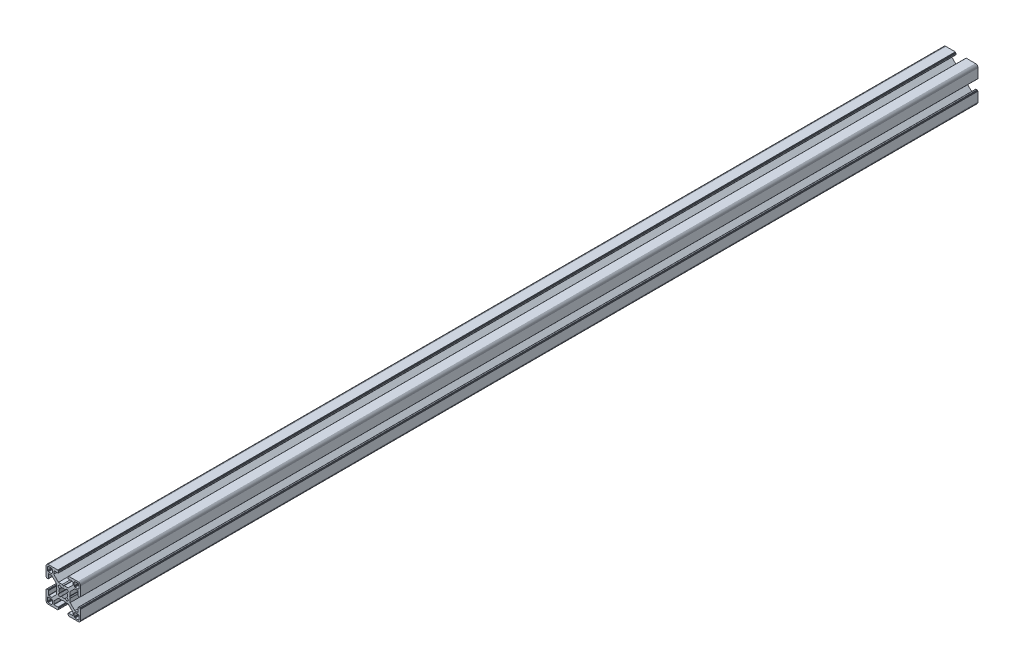
SolidWorks part; units mm, degrees
ref_plane "Front Plane" through (0, 0, 0) normal (0, 0, 1) x (1, 0, 0)
ref_plane "Top Plane" through (0, 0, 0) normal (0, 1, 0) x (1, 0, 0)
ref_plane "Right Plane" through (0, 0, 0) normal (1, 0, 0) x (0, 0, -1)
ref_plane "Plane1" through (0, 0, 0) normal (0, 0, 1) x (1, 0, 0)
sketch "Sketch1" plane through (0, 0, 0) normal (0, 0, 1) x (1, 0, 0)
  line L0 (28.3473, 29.9696) -> (28, 30)
  line L1 (28, 30) -> (19.75, 30)
  line L2 (19.75, 30) -> (19.7153, 29.997)
  line L3 (19.7153, 29.997) -> (19.6816, 29.9879)
  line L4 (19.6816, 29.9879) -> (19.65, 29.9732)
  line L5 (19.65, 29.9732) -> (19.6214, 29.9532)
  line L6 (19.6214, 29.9532) -> (19.5968, 29.9286)
  line L7 (19.5968, 29.9286) -> (19.5768, 29.9)
  line L8 (19.5768, 29.9) -> (19.5621, 29.8684)
  line L9 (19.5621, 29.8684) -> (19.553, 29.8347)
  line L10 (19.553, 29.8347) -> (19.55, 29.8)
  line L11 (19.55, 29.8) -> (19.55, 29.7)
  line L12 (19.55, 29.7) -> (19.547, 29.6653)
  line L13 (19.547, 29.6653) -> (19.5379, 29.6316)
  line L14 (19.5379, 29.6316) -> (19.5232, 29.6)
  line L15 (19.5232, 29.6) -> (19.5032, 29.5714)
  line L16 (19.5032, 29.5714) -> (19.4786, 29.5468)
  line L17 (19.4786, 29.5468) -> (19.45, 29.5268)
  line L18 (19.45, 29.5268) -> (19.4184, 29.5121)
  line L19 (19.4184, 29.5121) -> (19.3847, 29.503)
  line L20 (19.3847, 29.503) -> (19.35, 29.5)
  line L21 (19.35, 29.5) -> (19.25, 29.5)
  line L22 (19.25, 29.5) -> (19.2153, 29.497)
  line L23 (19.2153, 29.497) -> (19.1816, 29.4879)
  line L24 (19.1816, 29.4879) -> (19.15, 29.4732)
  line L25 (19.15, 29.4732) -> (19.1214, 29.4532)
  line L26 (19.1214, 29.4532) -> (19.0968, 29.4286)
  line L27 (19.0968, 29.4286) -> (19.0768, 29.4)
  line L28 (19.0768, 29.4) -> (19.0621, 29.3684)
  line L29 (19.0621, 29.3684) -> (19.053, 29.3347)
  line L30 (19.053, 29.3347) -> (19.05, 29.3)
  line L31 (19.05, 29.3) -> (19.05, 28.4)
  line L32 (19.05, 28.4) -> (19.0591, 28.2958)
  line L33 (19.0591, 28.2958) -> (19.0862, 28.1948)
  line L34 (19.0862, 28.1948) -> (19.1304, 28.1)
  line L35 (19.1304, 28.1) -> (19.1904, 28.0143)
  line L36 (19.1904, 28.0143) -> (19.2643, 27.9404)
  line L37 (19.2643, 27.9404) -> (19.35, 27.8804)
  line L38 (19.35, 27.8804) -> (19.4448, 27.8362)
  line L39 (19.4448, 27.8362) -> (19.5458, 27.8091)
  line L40 (19.5458, 27.8091) -> (19.65, 27.8)
  line L41 (19.65, 27.8) -> (23.05, 27.8)
  line L42 (23.05, 27.8) -> (23.0847, 27.7969)
  line L43 (23.0847, 27.7969) -> (23.1184, 27.7879)
  line L44 (23.1184, 27.7879) -> (23.15, 27.7732)
  line L45 (23.15, 27.7732) -> (23.1786, 27.7532)
  line L46 (23.1786, 27.7532) -> (23.2032, 27.7285)
  line L47 (23.2032, 27.7285) -> (23.2232, 27.7)
  line L48 (23.2232, 27.7) -> (23.2379, 27.6684)
  line L49 (23.2379, 27.6684) -> (23.247, 27.6347)
  line L50 (23.247, 27.6347) -> (23.25, 27.6)
  line L51 (23.25, 27.6) -> (23.25, 25.05)
  line L52 (23.25, 25.05) -> (19.2045, 21)
  line L53 (19.2045, 21) -> (15.9, 21)
  line L54 (15.9, 21) -> (15, 20.4848)
  line L55 (15, 20.4848) -> (14.1, 21)
  line L56 (14.1, 21) -> (10.7955, 21)
  line L57 (10.7955, 21) -> (7.9973, 23.8013)
  line L58 (7.9973, 23.8013) -> (6.75, 25.05)
  line L59 (6.75, 25.05) -> (6.75, 27.6)
  line L60 (6.75, 27.6) -> (6.753, 27.6347)
  line L61 (6.753, 27.6347) -> (6.7621, 27.6684)
  line L62 (6.7621, 27.6684) -> (6.7768, 27.7)
  line L63 (6.7768, 27.7) -> (6.7968, 27.7285)
  line L64 (6.7968, 27.7285) -> (6.8215, 27.7532)
  line L65 (6.8215, 27.7532) -> (6.85, 27.7732)
  line L66 (6.85, 27.7732) -> (6.8816, 27.7879)
  line L67 (6.8816, 27.7879) -> (6.9153, 27.7969)
  line L68 (6.9153, 27.7969) -> (6.95, 27.8)
  line L69 (6.95, 27.8) -> (10.35, 27.8)
  line L70 (10.35, 27.8) -> (10.4542, 27.8091)
  line L71 (10.4542, 27.8091) -> (10.5552, 27.8362)
  line L72 (10.5552, 27.8362) -> (10.65, 27.8804)
  line L73 (10.65, 27.8804) -> (10.7357, 27.9404)
  line L74 (10.7357, 27.9404) -> (10.8096, 28.0143)
  line L75 (10.8096, 28.0143) -> (10.8696, 28.1)
  line L76 (10.8696, 28.1) -> (10.9138, 28.1948)
  line L77 (10.9138, 28.1948) -> (10.9409, 28.2958)
  line L78 (10.9409, 28.2958) -> (10.95, 28.4)
  line L79 (10.95, 28.4) -> (10.95, 29.3)
  line L80 (10.95, 29.3) -> (10.947, 29.3347)
  line L81 (10.947, 29.3347) -> (10.938, 29.3684)
  line L82 (10.938, 29.3684) -> (10.9232, 29.4)
  line L83 (10.9232, 29.4) -> (10.9032, 29.4286)
  line L84 (10.9032, 29.4286) -> (10.8786, 29.4532)
  line L85 (10.8786, 29.4532) -> (10.85, 29.4732)
  line L86 (10.85, 29.4732) -> (10.8184, 29.4879)
  line L87 (10.8184, 29.4879) -> (10.7847, 29.497)
  line L88 (10.7847, 29.497) -> (10.75, 29.5)
  line L89 (10.75, 29.5) -> (10.65, 29.5)
  line L90 (10.65, 29.5) -> (10.6153, 29.503)
  line L91 (10.6153, 29.503) -> (10.5816, 29.5121)
  line L92 (10.5816, 29.5121) -> (10.55, 29.5268)
  line L93 (10.55, 29.5268) -> (10.5214, 29.5468)
  line L94 (10.5214, 29.5468) -> (10.4968, 29.5714)
  line L95 (10.4968, 29.5714) -> (10.4768, 29.6)
  line L96 (10.4768, 29.6) -> (10.4621, 29.6316)
  line L97 (10.4621, 29.6316) -> (10.453, 29.6653)
  line L98 (10.453, 29.6653) -> (10.45, 29.7)
  line L99 (10.45, 29.7) -> (10.45, 29.8)
  line L100 (10.45, 29.8) -> (10.447, 29.8347)
  line L101 (10.447, 29.8347) -> (10.4379, 29.8684)
  line L102 (10.4379, 29.8684) -> (10.4232, 29.9)
  line L103 (10.4232, 29.9) -> (10.4032, 29.9286)
  line L104 (10.4032, 29.9286) -> (10.3786, 29.9532)
  line L105 (10.3786, 29.9532) -> (10.35, 29.9732)
  line L106 (10.35, 29.9732) -> (10.3184, 29.9879)
  line L107 (10.3184, 29.9879) -> (10.2847, 29.997)
  line L108 (10.2847, 29.997) -> (10.25, 30)
  line L109 (10.25, 30) -> (2, 30)
  line L110 (2, 30) -> (1.6527, 29.9696)
  line L111 (1.6527, 29.9696) -> (1.316, 29.8794)
  line L112 (1.316, 29.8794) -> (1, 29.7321)
  line L113 (1, 29.7321) -> (0.7144, 29.5321)
  line L114 (0.7144, 29.5321) -> (0.4679, 29.2856)
  line L115 (0.4679, 29.2856) -> (0.2679, 29)
  line L116 (0.2679, 29) -> (0.1206, 28.684)
  line L117 (0.1206, 28.684) -> (0.0304, 28.3473)
  line L118 (0.0304, 28.3473) -> (0, 28)
  line L119 (0, 28) -> (0, 19.75)
  line L120 (0, 19.75) -> (0.003, 19.7153)
  line L121 (0.003, 19.7153) -> (0.0121, 19.6816)
  line L122 (0.0121, 19.6816) -> (0.0268, 19.65)
  line L123 (0.0268, 19.65) -> (0.0468, 19.6214)
  line L124 (0.0468, 19.6214) -> (0.0714, 19.5968)
  line L125 (0.0714, 19.5968) -> (0.1, 19.5768)
  line L126 (0.1, 19.5768) -> (0.1316, 19.5621)
  line L127 (0.1316, 19.5621) -> (0.1653, 19.553)
  line L128 (0.1653, 19.553) -> (0.2, 19.55)
  line L129 (0.2, 19.55) -> (0.3, 19.55)
  line L130 (0.3, 19.55) -> (0.3347, 19.547)
  line L131 (0.3347, 19.547) -> (0.3684, 19.5379)
  line L132 (0.3684, 19.5379) -> (0.4, 19.5232)
  line L133 (0.4, 19.5232) -> (0.4286, 19.5032)
  line L134 (0.4286, 19.5032) -> (0.4532, 19.4786)
  line L135 (0.4532, 19.4786) -> (0.4732, 19.45)
  line L136 (0.4732, 19.45) -> (0.4879, 19.4184)
  line L137 (0.4879, 19.4184) -> (0.497, 19.3847)
  line L138 (0.497, 19.3847) -> (0.5, 19.35)
  line L139 (0.5, 19.35) -> (0.5, 19.25)
  line L140 (0.5, 19.25) -> (0.503, 19.2153)
  line L141 (0.503, 19.2153) -> (0.5121, 19.1816)
  line L142 (0.5121, 19.1816) -> (0.5268, 19.15)
  line L143 (0.5268, 19.15) -> (0.5468, 19.1214)
  line L144 (0.5468, 19.1214) -> (0.5714, 19.0968)
  line L145 (0.5714, 19.0968) -> (0.6, 19.0768)
  line L146 (0.6, 19.0768) -> (0.6316, 19.0621)
  line L147 (0.6316, 19.0621) -> (0.6653, 19.053)
  line L148 (0.6653, 19.053) -> (0.7, 19.05)
  line L149 (0.7, 19.05) -> (1.6, 19.05)
  line L150 (1.6, 19.05) -> (1.7042, 19.0591)
  line L151 (1.7042, 19.0591) -> (1.8052, 19.0862)
  line L152 (1.8052, 19.0862) -> (1.9, 19.1304)
  line L153 (1.9, 19.1304) -> (1.9857, 19.1904)
  line L154 (1.9857, 19.1904) -> (2.0596, 19.2643)
  line L155 (2.0596, 19.2643) -> (2.1196, 19.35)
  line L156 (2.1196, 19.35) -> (2.1638, 19.4448)
  line L157 (2.1638, 19.4448) -> (2.1909, 19.5458)
  line L158 (2.1909, 19.5458) -> (2.2, 19.65)
  line L159 (2.2, 19.65) -> (2.2, 23.05)
  line L160 (2.2, 23.05) -> (2.203, 23.0847)
  line L161 (2.203, 23.0847) -> (2.2121, 23.1184)
  line L162 (2.2121, 23.1184) -> (2.2268, 23.15)
  line L163 (2.2268, 23.15) -> (2.2468, 23.1786)
  line L164 (2.2468, 23.1786) -> (2.2714, 23.2032)
  line L165 (2.2714, 23.2032) -> (2.3, 23.2232)
  line L166 (2.3, 23.2232) -> (2.3316, 23.2379)
  line L167 (2.3316, 23.2379) -> (2.3653, 23.247)
  line L168 (2.3653, 23.247) -> (2.4, 23.25)
  line L169 (2.4, 23.25) -> (4.95, 23.25)
  line L170 (4.95, 23.25) -> (7.9973, 20.2027)
  line L171 (7.9973, 20.2027) -> (8.9955, 19.2045)
  line L172 (8.9955, 19.2045) -> (8.9955, 15.9)
  line L173 (8.9955, 15.9) -> (9.5151, 15)
  line L174 (9.5151, 15) -> (8.9955, 14.1)
  line L175 (8.9955, 14.1) -> (8.9955, 10.7955)
  line L176 (8.9955, 10.7955) -> (4.95, 6.75)
  line L177 (4.95, 6.75) -> (2.4, 6.75)
  line L178 (2.4, 6.75) -> (2.3653, 6.753)
  line L179 (2.3653, 6.753) -> (2.3316, 6.7621)
  line L180 (2.3316, 6.7621) -> (2.3, 6.7768)
  line L181 (2.3, 6.7768) -> (2.2714, 6.7968)
  line L182 (2.2714, 6.7968) -> (2.2468, 6.8214)
  line L183 (2.2468, 6.8214) -> (2.2268, 6.85)
  line L184 (2.2268, 6.85) -> (2.2121, 6.8816)
  line L185 (2.2121, 6.8816) -> (2.203, 6.9153)
  line L186 (2.203, 6.9153) -> (2.2, 6.95)
  line L187 (2.2, 6.95) -> (2.2, 10.35)
  line L188 (2.2, 10.35) -> (2.1909, 10.4542)
  line L189 (2.1909, 10.4542) -> (2.1638, 10.5552)
  line L190 (2.1638, 10.5552) -> (2.1196, 10.65)
  line L191 (2.1196, 10.65) -> (2.0596, 10.7357)
  line L192 (2.0596, 10.7357) -> (1.9857, 10.8096)
  line L193 (1.9857, 10.8096) -> (1.9, 10.8696)
  line L194 (1.9, 10.8696) -> (1.8052, 10.9138)
  line L195 (1.8052, 10.9138) -> (1.7042, 10.9409)
  line L196 (1.7042, 10.9409) -> (1.6, 10.95)
  line L197 (1.6, 10.95) -> (0.7, 10.95)
  line L198 (0.7, 10.95) -> (0.6653, 10.9469)
  line L199 (0.6653, 10.9469) -> (0.6316, 10.9379)
  line L200 (0.6316, 10.9379) -> (0.6, 10.9232)
  line L201 (0.6, 10.9232) -> (0.5715, 10.9032)
  line L202 (0.5715, 10.9032) -> (0.5468, 10.8785)
  line L203 (0.5468, 10.8785) -> (0.5268, 10.85)
  line L204 (0.5268, 10.85) -> (0.5121, 10.8184)
  line L205 (0.5121, 10.8184) -> (0.503, 10.7847)
  line L206 (0.503, 10.7847) -> (0.5, 10.75)
  line L207 (0.5, 10.75) -> (0.5, 10.65)
  line L208 (0.5, 10.65) -> (0.497, 10.6153)
  line L209 (0.497, 10.6153) -> (0.4879, 10.5816)
  line L210 (0.4879, 10.5816) -> (0.4732, 10.55)
  line L211 (0.4732, 10.55) -> (0.4532, 10.5214)
  line L212 (0.4532, 10.5214) -> (0.4286, 10.4968)
  line L213 (0.4286, 10.4968) -> (0.4, 10.4768)
  line L214 (0.4, 10.4768) -> (0.3684, 10.4621)
  line L215 (0.3684, 10.4621) -> (0.3347, 10.453)
  line L216 (0.3347, 10.453) -> (0.3, 10.45)
  line L217 (0.3, 10.45) -> (0.2, 10.45)
  line L218 (0.2, 10.45) -> (0.1653, 10.447)
  line L219 (0.1653, 10.447) -> (0.1316, 10.4379)
  line L220 (0.1316, 10.4379) -> (0.1, 10.4232)
  line L221 (0.1, 10.4232) -> (0.0714, 10.4032)
  line L222 (0.0714, 10.4032) -> (0.0468, 10.3786)
  line L223 (0.0468, 10.3786) -> (0.0268, 10.35)
  line L224 (0.0268, 10.35) -> (0.0121, 10.3184)
  line L225 (0.0121, 10.3184) -> (0.003, 10.2847)
  line L226 (0.003, 10.2847) -> (0, 10.25)
  line L227 (0, 10.25) -> (0, 2)
  line L228 (0, 2) -> (0.0304, 1.6527)
  line L229 (0.0304, 1.6527) -> (0.1206, 1.316)
  line L230 (0.1206, 1.316) -> (0.2679, 1)
  line L231 (0.2679, 1) -> (0.4679, 0.7144)
  line L232 (0.4679, 0.7144) -> (0.7144, 0.4679)
  line L233 (0.7144, 0.4679) -> (1, 0.2679)
  line L234 (1, 0.2679) -> (1.316, 0.1206)
  line L235 (1.316, 0.1206) -> (1.6527, 0.0304)
  line L236 (1.6527, 0.0304) -> (2, 0)
  line L237 (2, 0) -> (10.25, 0)
  line L238 (10.25, 0) -> (10.2847, 0.003)
  line L239 (10.2847, 0.003) -> (10.3184, 0.0121)
  line L240 (10.3184, 0.0121) -> (10.35, 0.0268)
  line L241 (10.35, 0.0268) -> (10.3786, 0.0468)
  line L242 (10.3786, 0.0468) -> (10.4032, 0.0714)
  line L243 (10.4032, 0.0714) -> (10.4232, 0.1)
  line L244 (10.4232, 0.1) -> (10.4379, 0.1316)
  line L245 (10.4379, 0.1316) -> (10.447, 0.1653)
  line L246 (10.447, 0.1653) -> (10.45, 0.2)
  line L247 (10.45, 0.2) -> (10.45, 0.3)
  line L248 (10.45, 0.3) -> (10.453, 0.3347)
  line L249 (10.453, 0.3347) -> (10.4621, 0.3684)
  line L250 (10.4621, 0.3684) -> (10.4768, 0.4)
  line L251 (10.4768, 0.4) -> (10.4968, 0.4286)
  line L252 (10.4968, 0.4286) -> (10.5214, 0.4532)
  line L253 (10.5214, 0.4532) -> (10.55, 0.4732)
  line L254 (10.55, 0.4732) -> (10.5816, 0.4879)
  line L255 (10.5816, 0.4879) -> (10.6153, 0.497)
  line L256 (10.6153, 0.497) -> (10.65, 0.5)
  line L257 (10.65, 0.5) -> (10.75, 0.5)
  line L258 (10.75, 0.5) -> (10.7847, 0.503)
  line L259 (10.7847, 0.503) -> (10.8184, 0.5121)
  line L260 (10.8184, 0.5121) -> (10.85, 0.5268)
  line L261 (10.85, 0.5268) -> (10.8785, 0.5468)
  line L262 (10.8785, 0.5468) -> (10.9032, 0.5715)
  line L263 (10.9032, 0.5715) -> (10.9232, 0.6)
  line L264 (10.9232, 0.6) -> (10.9379, 0.6316)
  line L265 (10.9379, 0.6316) -> (10.9469, 0.6653)
  line L266 (10.9469, 0.6653) -> (10.95, 0.7)
  line L267 (10.95, 0.7) -> (10.95, 1.6)
  line L268 (10.95, 1.6) -> (10.9409, 1.7042)
  line L269 (10.9409, 1.7042) -> (10.9138, 1.8052)
  line L270 (10.9138, 1.8052) -> (10.8696, 1.9)
  line L271 (10.8696, 1.9) -> (10.8096, 1.9857)
  line L272 (10.8096, 1.9857) -> (10.7357, 2.0596)
  line L273 (10.7357, 2.0596) -> (10.65, 2.1196)
  line L274 (10.65, 2.1196) -> (10.5552, 2.1638)
  line L275 (10.5552, 2.1638) -> (10.4542, 2.1909)
  line L276 (10.4542, 2.1909) -> (10.35, 2.2)
  line L277 (10.35, 2.2) -> (6.95, 2.2)
  line L278 (6.95, 2.2) -> (6.9153, 2.203)
  line L279 (6.9153, 2.203) -> (6.8816, 2.212)
  line L280 (6.8816, 2.212) -> (6.85, 2.2268)
  line L281 (6.85, 2.2268) -> (6.8215, 2.2468)
  line L282 (6.8215, 2.2468) -> (6.7968, 2.2714)
  line L283 (6.7968, 2.2714) -> (6.7768, 2.3)
  line L284 (6.7768, 2.3) -> (6.7621, 2.3316)
  line L285 (6.7621, 2.3316) -> (6.753, 2.3653)
  line L286 (6.753, 2.3653) -> (6.75, 2.4)
  line L287 (6.75, 2.4) -> (6.75, 4.95)
  line L288 (6.75, 4.95) -> (9.7875, 7.9908)
  line L289 (9.7875, 7.9908) -> (10.7955, 9)
  line L290 (10.7955, 9) -> (14.1, 9)
  line L291 (14.1, 9) -> (15, 9.5151)
  line L292 (15, 9.5151) -> (15.9, 9)
  line L293 (15.9, 9) -> (19.2045, 9)
  line L294 (19.2045, 9) -> (20.2126, 7.9908)
  line L295 (20.2126, 7.9908) -> (23.25, 4.95)
  line L296 (23.25, 4.95) -> (23.25, 2.4)
  line L297 (23.25, 2.4) -> (23.247, 2.3653)
  line L298 (23.247, 2.3653) -> (23.2379, 2.3316)
  line L299 (23.2379, 2.3316) -> (23.2232, 2.3)
  line L300 (23.2232, 2.3) -> (23.2032, 2.2714)
  line L301 (23.2032, 2.2714) -> (23.1786, 2.2468)
  line L302 (23.1786, 2.2468) -> (23.15, 2.2268)
  line L303 (23.15, 2.2268) -> (23.1184, 2.212)
  line L304 (23.1184, 2.212) -> (23.0847, 2.203)
  line L305 (23.0847, 2.203) -> (23.05, 2.2)
  line L306 (23.05, 2.2) -> (19.65, 2.2)
  line L307 (19.65, 2.2) -> (19.5458, 2.1909)
  line L308 (19.5458, 2.1909) -> (19.4448, 2.1638)
  line L309 (19.4448, 2.1638) -> (19.35, 2.1196)
  line L310 (19.35, 2.1196) -> (19.2643, 2.0596)
  line L311 (19.2643, 2.0596) -> (19.1904, 1.9857)
  line L312 (19.1904, 1.9857) -> (19.1304, 1.9)
  line L313 (19.1304, 1.9) -> (19.0862, 1.8052)
  line L314 (19.0862, 1.8052) -> (19.0591, 1.7042)
  line L315 (19.0591, 1.7042) -> (19.05, 1.6)
  line L316 (19.05, 1.6) -> (19.05, 0.7)
  line L317 (19.05, 0.7) -> (19.053, 0.6653)
  line L318 (19.053, 0.6653) -> (19.0621, 0.6316)
  line L319 (19.0621, 0.6316) -> (19.0768, 0.6)
  line L320 (19.0768, 0.6) -> (19.0968, 0.5714)
  line L321 (19.0968, 0.5714) -> (19.1214, 0.5468)
  line L322 (19.1214, 0.5468) -> (19.15, 0.5268)
  line L323 (19.15, 0.5268) -> (19.1816, 0.5121)
  line L324 (19.1816, 0.5121) -> (19.2153, 0.503)
  line L325 (19.2153, 0.503) -> (19.25, 0.5)
  line L326 (19.25, 0.5) -> (19.35, 0.5)
  line L327 (19.35, 0.5) -> (19.3847, 0.497)
  line L328 (19.3847, 0.497) -> (19.4184, 0.4879)
  line L329 (19.4184, 0.4879) -> (19.45, 0.4732)
  line L330 (19.45, 0.4732) -> (19.4786, 0.4532)
  line L331 (19.4786, 0.4532) -> (19.5032, 0.4286)
  line L332 (19.5032, 0.4286) -> (19.5232, 0.4)
  line L333 (19.5232, 0.4) -> (19.5379, 0.3684)
  line L334 (19.5379, 0.3684) -> (19.547, 0.3347)
  line L335 (19.547, 0.3347) -> (19.55, 0.3)
  line L336 (19.55, 0.3) -> (19.55, 0.2)
  line L337 (19.55, 0.2) -> (19.553, 0.1653)
  line L338 (19.553, 0.1653) -> (19.5621, 0.1316)
  line L339 (19.5621, 0.1316) -> (19.5768, 0.1)
  line L340 (19.5768, 0.1) -> (19.5968, 0.0714)
  line L341 (19.5968, 0.0714) -> (19.6214, 0.0468)
  line L342 (19.6214, 0.0468) -> (19.65, 0.0268)
  line L343 (19.65, 0.0268) -> (19.6816, 0.0121)
  line L344 (19.6816, 0.0121) -> (19.7153, 0.003)
  line L345 (19.7153, 0.003) -> (19.75, 0)
  line L346 (19.75, 0) -> (28, 0)
  line L347 (28, 0) -> (28.3473, 0.0304)
  line L348 (28.3473, 0.0304) -> (28.684, 0.1206)
  line L349 (28.684, 0.1206) -> (29, 0.2679)
  line L350 (29, 0.2679) -> (29.2856, 0.4679)
  line L351 (29.2856, 0.4679) -> (29.5321, 0.7144)
  line L352 (29.5321, 0.7144) -> (29.7321, 1)
  line L353 (29.7321, 1) -> (29.8794, 1.316)
  line L354 (29.8794, 1.316) -> (29.9696, 1.6527)
  line L355 (29.9696, 1.6527) -> (30, 2)
  line L356 (30, 2) -> (30, 10.25)
  line L357 (30, 10.25) -> (29.997, 10.2847)
  line L358 (29.997, 10.2847) -> (29.988, 10.3184)
  line L359 (29.988, 10.3184) -> (29.9732, 10.35)
  line L360 (29.9732, 10.35) -> (29.9532, 10.3785)
  line L361 (29.9532, 10.3785) -> (29.9286, 10.4032)
  line L362 (29.9286, 10.4032) -> (29.9, 10.4232)
  line L363 (29.9, 10.4232) -> (29.8684, 10.4379)
  line L364 (29.8684, 10.4379) -> (29.8347, 10.447)
  line L365 (29.8347, 10.447) -> (29.8, 10.45)
  line L366 (29.8, 10.45) -> (29.7, 10.45)
  line L367 (29.7, 10.45) -> (29.6649, 10.4534)
  line L368 (29.6649, 10.4534) -> (29.6312, 10.4624)
  line L369 (29.6312, 10.4624) -> (29.5996, 10.4772)
  line L370 (29.5996, 10.4772) -> (29.5711, 10.4972)
  line L371 (29.5711, 10.4972) -> (29.5464, 10.5218)
  line L372 (29.5464, 10.5218) -> (29.5264, 10.5504)
  line L373 (29.5264, 10.5504) -> (29.5117, 10.582)
  line L374 (29.5117, 10.582) -> (29.5027, 10.6156)
  line L375 (29.5027, 10.6156) -> (29.4996, 10.6504)
  line L376 (29.4996, 10.6504) -> (29.4996, 10.7504)
  line L377 (29.4996, 10.7504) -> (29.497, 10.7847)
  line L378 (29.497, 10.7847) -> (29.4879, 10.8184)
  line L379 (29.4879, 10.8184) -> (29.4732, 10.85)
  line L380 (29.4732, 10.85) -> (29.4532, 10.8785)
  line L381 (29.4532, 10.8785) -> (29.4286, 10.9032)
  line L382 (29.4286, 10.9032) -> (29.4, 10.9232)
  line L383 (29.4, 10.9232) -> (29.3684, 10.9379)
  line L384 (29.3684, 10.9379) -> (29.3347, 10.9469)
  line L385 (29.3347, 10.9469) -> (29.3, 10.95)
  line L386 (29.3, 10.95) -> (28.4, 10.95)
  line L387 (28.4, 10.95) -> (28.2958, 10.9409)
  line L388 (28.2958, 10.9409) -> (28.1948, 10.9138)
  line L389 (28.1948, 10.9138) -> (28.1, 10.8696)
  line L390 (28.1, 10.8696) -> (28.0143, 10.8096)
  line L391 (28.0143, 10.8096) -> (27.9404, 10.7357)
  line L392 (27.9404, 10.7357) -> (27.8804, 10.65)
  line L393 (27.8804, 10.65) -> (27.8362, 10.5552)
  line L394 (27.8362, 10.5552) -> (27.8091, 10.4542)
  line L395 (27.8091, 10.4542) -> (27.8, 10.35)
  line L396 (27.8, 10.35) -> (27.8, 6.95)
  line L397 (27.8, 6.95) -> (27.797, 6.9153)
  line L398 (27.797, 6.9153) -> (27.7879, 6.8816)
  line L399 (27.7879, 6.8816) -> (27.7732, 6.85)
  line L400 (27.7732, 6.85) -> (27.7532, 6.8214)
  line L401 (27.7532, 6.8214) -> (27.7286, 6.7968)
  line L402 (27.7286, 6.7968) -> (27.7, 6.7768)
  line L403 (27.7, 6.7768) -> (27.6684, 6.7621)
  line L404 (27.6684, 6.7621) -> (27.6347, 6.753)
  line L405 (27.6347, 6.753) -> (27.6, 6.75)
  line L406 (27.6, 6.75) -> (25.05, 6.75)
  line L407 (25.05, 6.75) -> (23.8092, 7.9908)
  line L408 (23.8092, 7.9908) -> (21.0045, 10.7955)
  line L409 (21.0045, 10.7955) -> (21.0045, 14.1)
  line L410 (21.0045, 14.1) -> (20.4849, 15)
  line L411 (20.4849, 15) -> (21.0045, 15.9)
  line L412 (21.0045, 15.9) -> (21.0045, 19.2045)
  line L413 (21.0045, 19.2045) -> (25.05, 23.25)
  line L414 (25.05, 23.25) -> (27.6, 23.25)
  line L415 (27.6, 23.25) -> (27.6347, 23.247)
  line L416 (27.6347, 23.247) -> (27.6684, 23.2379)
  line L417 (27.6684, 23.2379) -> (27.7, 23.2232)
  line L418 (27.7, 23.2232) -> (27.7286, 23.2032)
  line L419 (27.7286, 23.2032) -> (27.7532, 23.1786)
  line L420 (27.7532, 23.1786) -> (27.7732, 23.15)
  line L421 (27.7732, 23.15) -> (27.7879, 23.1184)
  line L422 (27.7879, 23.1184) -> (27.797, 23.0847)
  line L423 (27.797, 23.0847) -> (27.8, 23.05)
  line L424 (27.8, 23.05) -> (27.8, 19.65)
  line L425 (27.8, 19.65) -> (27.8091, 19.5458)
  line L426 (27.8091, 19.5458) -> (27.8362, 19.4448)
  line L427 (27.8362, 19.4448) -> (27.8804, 19.35)
  line L428 (27.8804, 19.35) -> (27.9404, 19.2643)
  line L429 (27.9404, 19.2643) -> (28.0143, 19.1904)
  line L430 (28.0143, 19.1904) -> (28.1, 19.1304)
  line L431 (28.1, 19.1304) -> (28.1948, 19.0862)
  line L432 (28.1948, 19.0862) -> (28.2958, 19.0591)
  line L433 (28.2958, 19.0591) -> (28.4, 19.05)
  line L434 (28.4, 19.05) -> (29.3, 19.05)
  line L435 (29.3, 19.05) -> (29.3347, 19.053)
  line L436 (29.3347, 19.053) -> (29.3684, 19.0621)
  line L437 (29.3684, 19.0621) -> (29.4, 19.0768)
  line L438 (29.4, 19.0768) -> (29.4282, 19.0971)
  line L439 (29.4282, 19.0971) -> (29.4528, 19.1218)
  line L440 (29.4528, 19.1218) -> (29.4728, 19.1504)
  line L441 (29.4728, 19.1504) -> (29.4876, 19.182)
  line L442 (29.4876, 19.182) -> (29.4966, 19.2156)
  line L443 (29.4966, 19.2156) -> (29.4996, 19.2504)
  line L444 (29.4996, 19.2504) -> (29.4996, 19.3504)
  line L445 (29.4996, 19.3504) -> (29.5027, 19.3851)
  line L446 (29.5027, 19.3851) -> (29.5117, 19.4188)
  line L447 (29.5117, 19.4188) -> (29.5264, 19.4504)
  line L448 (29.5264, 19.4504) -> (29.5464, 19.4789)
  line L449 (29.5464, 19.4789) -> (29.5711, 19.5036)
  line L450 (29.5711, 19.5036) -> (29.5996, 19.5236)
  line L451 (29.5996, 19.5236) -> (29.6312, 19.5383)
  line L452 (29.6312, 19.5383) -> (29.6649, 19.5473)
  line L453 (29.6649, 19.5473) -> (29.7, 19.55)
  line L454 (29.7, 19.55) -> (29.8, 19.55)
  line L455 (29.8, 19.55) -> (29.8347, 19.553)
  line L456 (29.8347, 19.553) -> (29.8684, 19.5621)
  line L457 (29.8684, 19.5621) -> (29.9, 19.5768)
  line L458 (29.9, 19.5768) -> (29.9286, 19.5968)
  line L459 (29.9286, 19.5968) -> (29.9532, 19.6214)
  line L460 (29.9532, 19.6214) -> (29.9732, 19.65)
  line L461 (29.9732, 19.65) -> (29.9879, 19.6816)
  line L462 (29.9879, 19.6816) -> (29.997, 19.7153)
  line L463 (29.997, 19.7153) -> (30, 19.75)
  line L464 (30, 19.75) -> (30, 28)
  line L465 (30, 28) -> (29.9696, 28.3473)
  line L466 (29.9696, 28.3473) -> (29.8794, 28.684)
  line L467 (29.8794, 28.684) -> (29.7321, 29)
  line L468 (29.7321, 29) -> (29.5321, 29.2856)
  line L469 (29.5321, 29.2856) -> (29.2856, 29.5321)
  line L470 (29.2856, 29.5321) -> (29, 29.7321)
  line L471 (29, 29.7321) -> (28.684, 29.8794)
  line L472 (28.684, 29.8794) -> (28.3473, 29.9696)
  line L473 (1.3, 25.5) -> (1.3, 27.7)
  line L474 (1.3, 27.7) -> (1.3123, 27.8564)
  line L475 (1.3123, 27.8564) -> (1.3489, 28.009)
  line L476 (1.3489, 28.009) -> (1.409, 28.154)
  line L477 (1.409, 28.154) -> (1.491, 28.2878)
  line L478 (1.491, 28.2878) -> (1.5929, 28.4071)
  line L479 (1.5929, 28.4071) -> (1.7122, 28.509)
  line L480 (1.7122, 28.509) -> (1.846, 28.591)
  line L481 (1.846, 28.591) -> (1.991, 28.6511)
  line L482 (1.991, 28.6511) -> (2.1436, 28.6877)
  line L483 (2.1436, 28.6877) -> (2.3, 28.7)
  line L484 (2.3, 28.7) -> (4.5, 28.7)
  line L485 (4.5, 28.7) -> (4.6564, 28.6877)
  line L486 (4.6564, 28.6877) -> (4.809, 28.6511)
  line L487 (4.809, 28.6511) -> (4.954, 28.591)
  line L488 (4.954, 28.591) -> (5.0878, 28.509)
  line L489 (5.0878, 28.509) -> (5.2071, 28.4071)
  line L490 (5.2071, 28.4071) -> (5.309, 28.2878)
  line L491 (5.309, 28.2878) -> (5.391, 28.154)
  line L492 (5.391, 28.154) -> (5.4511, 28.009)
  line L493 (5.4511, 28.009) -> (5.4877, 27.8564)
  line L494 (5.4877, 27.8564) -> (5.5, 27.7)
  line L495 (5.5, 27.7) -> (5.5, 25.5)
  line L496 (5.5, 25.5) -> (5.4877, 25.3436)
  line L497 (5.4877, 25.3436) -> (5.4511, 25.191)
  line L498 (5.4511, 25.191) -> (5.391, 25.046)
  line L499 (5.391, 25.046) -> (5.309, 24.9122)
  line L500 (5.309, 24.9122) -> (5.2071, 24.7929)
  line L501 (5.2071, 24.7929) -> (5.0878, 24.691)
  line L502 (5.0878, 24.691) -> (4.954, 24.609)
  line L503 (4.954, 24.609) -> (4.809, 24.5489)
  line L504 (4.809, 24.5489) -> (4.6564, 24.5123)
  line L505 (4.6564, 24.5123) -> (4.5, 24.5)
  line L506 (4.5, 24.5) -> (2.3, 24.5)
  line L507 (2.3, 24.5) -> (2.1436, 24.5123)
  line L508 (2.1436, 24.5123) -> (1.991, 24.5489)
  line L509 (1.991, 24.5489) -> (1.846, 24.609)
  line L510 (1.846, 24.609) -> (1.7122, 24.691)
  line L511 (1.7122, 24.691) -> (1.5929, 24.7929)
  line L512 (1.5929, 24.7929) -> (1.491, 24.9122)
  line L513 (1.491, 24.9122) -> (1.409, 25.046)
  line L514 (1.409, 25.046) -> (1.3489, 25.191)
  line L515 (1.3489, 25.191) -> (1.3123, 25.3436)
  line L516 (1.3123, 25.3436) -> (1.3, 25.5)
  line L517 (25.3436, 28.6877) -> (25.5, 28.7)
  line L518 (25.5, 28.7) -> (27.7, 28.7)
  line L519 (27.7, 28.7) -> (27.8564, 28.6877)
  line L520 (27.8564, 28.6877) -> (28.009, 28.6511)
  line L521 (28.009, 28.6511) -> (28.154, 28.591)
  line L522 (28.154, 28.591) -> (28.2878, 28.509)
  line L523 (28.2878, 28.509) -> (28.4071, 28.4071)
  line L524 (28.4071, 28.4071) -> (28.509, 28.2878)
  line L525 (28.509, 28.2878) -> (28.591, 28.154)
  line L526 (28.591, 28.154) -> (28.6511, 28.009)
  line L527 (28.6511, 28.009) -> (28.6877, 27.8564)
  line L528 (28.6877, 27.8564) -> (28.7, 27.7)
  line L529 (28.7, 27.7) -> (28.7, 25.5)
  line L530 (28.7, 25.5) -> (28.6877, 25.3436)
  line L531 (28.6877, 25.3436) -> (28.6511, 25.191)
  line L532 (28.6511, 25.191) -> (28.591, 25.046)
  line L533 (28.591, 25.046) -> (28.509, 24.9122)
  line L534 (28.509, 24.9122) -> (28.4071, 24.7929)
  line L535 (28.4071, 24.7929) -> (28.2878, 24.691)
  line L536 (28.2878, 24.691) -> (28.154, 24.609)
  line L537 (28.154, 24.609) -> (28.009, 24.5489)
  line L538 (28.009, 24.5489) -> (27.8564, 24.5123)
  line L539 (27.8564, 24.5123) -> (27.7, 24.5)
  line L540 (27.7, 24.5) -> (25.5, 24.5)
  line L541 (25.5, 24.5) -> (25.3436, 24.5123)
  line L542 (25.3436, 24.5123) -> (25.191, 24.5489)
  line L543 (25.191, 24.5489) -> (25.046, 24.609)
  line L544 (25.046, 24.609) -> (24.9122, 24.691)
  line L545 (24.9122, 24.691) -> (24.7929, 24.7929)
  line L546 (24.7929, 24.7929) -> (24.691, 24.9122)
  line L547 (24.691, 24.9122) -> (24.609, 25.046)
  line L548 (24.609, 25.046) -> (24.5489, 25.191)
  line L549 (24.5489, 25.191) -> (24.5123, 25.3436)
  line L550 (24.5123, 25.3436) -> (24.5, 25.5)
  line L551 (24.5, 25.5) -> (24.5, 27.7)
  line L552 (24.5, 27.7) -> (24.5123, 27.8564)
  line L553 (24.5123, 27.8564) -> (24.5489, 28.009)
  line L554 (24.5489, 28.009) -> (24.609, 28.154)
  line L555 (24.609, 28.154) -> (24.691, 28.2878)
  line L556 (24.691, 28.2878) -> (24.7929, 28.4071)
  line L557 (24.7929, 28.4071) -> (24.9122, 28.509)
  line L558 (24.9122, 28.509) -> (25.046, 28.591)
  line L559 (25.046, 28.591) -> (25.191, 28.6511)
  line L560 (25.191, 28.6511) -> (25.3436, 28.6877)
  line L561 (15, 18.65) -> (15.55, 18.6083)
  line L562 (15.55, 18.6083) -> (16.0875, 18.4842)
  line L563 (16.0875, 18.4842) -> (16.6001, 18.2806)
  line L564 (16.6001, 18.2806) -> (18.1359, 19.5184)
  line L565 (18.1359, 19.5184) -> (18.645, 19.1187)
  line L566 (18.645, 19.1187) -> (19.1036, 18.6621)
  line L567 (19.1036, 18.6621) -> (19.5053, 18.1547)
  line L568 (19.5053, 18.1547) -> (18.2806, 16.6001)
  line L569 (18.2806, 16.6001) -> (18.4842, 16.0875)
  line L570 (18.4842, 16.0875) -> (18.6083, 15.55)
  line L571 (18.6083, 15.55) -> (18.65, 15)
  line L572 (18.65, 15) -> (18.6083, 14.45)
  line L573 (18.6083, 14.45) -> (18.4842, 13.9125)
  line L574 (18.4842, 13.9125) -> (18.2806, 13.3999)
  line L575 (18.2806, 13.3999) -> (19.5053, 11.8453)
  line L576 (19.5053, 11.8453) -> (19.1036, 11.3379)
  line L577 (19.1036, 11.3379) -> (18.645, 10.8813)
  line L578 (18.645, 10.8813) -> (18.1359, 10.4816)
  line L579 (18.1359, 10.4816) -> (16.6001, 11.7194)
  line L580 (16.6001, 11.7194) -> (16.0875, 11.5158)
  line L581 (16.0875, 11.5158) -> (15.55, 11.3917)
  line L582 (15.55, 11.3917) -> (15, 11.35)
  line L583 (15, 11.35) -> (14.45, 11.3917)
  line L584 (14.45, 11.3917) -> (13.9125, 11.5158)
  line L585 (13.9125, 11.5158) -> (13.3999, 11.7194)
  line L586 (13.3999, 11.7194) -> (11.8641, 10.4816)
  line L587 (11.8641, 10.4816) -> (11.355, 10.8813)
  line L588 (11.355, 10.8813) -> (10.8964, 11.3379)
  line L589 (10.8964, 11.3379) -> (10.4947, 11.8453)
  line L590 (10.4947, 11.8453) -> (11.7194, 13.3999)
  line L591 (11.7194, 13.3999) -> (11.5158, 13.9125)
  line L592 (11.5158, 13.9125) -> (11.3917, 14.45)
  line L593 (11.3917, 14.45) -> (11.35, 15)
  line L594 (11.35, 15) -> (11.3917, 15.55)
  line L595 (11.3917, 15.55) -> (11.5158, 16.0875)
  line L596 (11.5158, 16.0875) -> (11.7194, 16.6001)
  line L597 (11.7194, 16.6001) -> (10.4947, 18.1547)
  line L598 (10.4947, 18.1547) -> (10.8964, 18.6621)
  line L599 (10.8964, 18.6621) -> (11.355, 19.1187)
  line L600 (11.355, 19.1187) -> (11.8641, 19.5184)
  line L601 (11.8641, 19.5184) -> (13.3999, 18.2806)
  line L602 (13.3999, 18.2806) -> (13.9125, 18.4842)
  line L603 (13.9125, 18.4842) -> (14.45, 18.6083)
  line L604 (14.45, 18.6083) -> (15, 18.65)
  line L605 (4.5, 1.3) -> (2.3, 1.3)
  line L606 (2.3, 1.3) -> (2.1436, 1.3123)
  line L607 (2.1436, 1.3123) -> (1.991, 1.3489)
  line L608 (1.991, 1.3489) -> (1.846, 1.409)
  line L609 (1.846, 1.409) -> (1.7122, 1.491)
  line L610 (1.7122, 1.491) -> (1.5929, 1.5929)
  line L611 (1.5929, 1.5929) -> (1.491, 1.7122)
  line L612 (1.491, 1.7122) -> (1.409, 1.846)
  line L613 (1.409, 1.846) -> (1.3489, 1.991)
  line L614 (1.3489, 1.991) -> (1.3123, 2.1436)
  line L615 (1.3123, 2.1436) -> (1.3, 2.3)
  line L616 (1.3, 2.3) -> (1.3, 4.5)
  line L617 (1.3, 4.5) -> (1.3123, 4.6564)
  line L618 (1.3123, 4.6564) -> (1.3489, 4.809)
  line L619 (1.3489, 4.809) -> (1.409, 4.954)
  line L620 (1.409, 4.954) -> (1.491, 5.0878)
  line L621 (1.491, 5.0878) -> (1.5929, 5.2071)
  line L622 (1.5929, 5.2071) -> (1.7122, 5.309)
  line L623 (1.7122, 5.309) -> (1.846, 5.391)
  line L624 (1.846, 5.391) -> (1.991, 5.4511)
  line L625 (1.991, 5.4511) -> (2.1436, 5.4877)
  line L626 (2.1436, 5.4877) -> (2.3, 5.5)
  line L627 (2.3, 5.5) -> (4.5, 5.5)
  line L628 (4.5, 5.5) -> (4.6564, 5.4877)
  line L629 (4.6564, 5.4877) -> (4.809, 5.4511)
  line L630 (4.809, 5.4511) -> (4.954, 5.391)
  line L631 (4.954, 5.391) -> (5.0878, 5.309)
  line L632 (5.0878, 5.309) -> (5.2071, 5.2071)
  line L633 (5.2071, 5.2071) -> (5.309, 5.0878)
  line L634 (5.309, 5.0878) -> (5.391, 4.954)
  line L635 (5.391, 4.954) -> (5.4511, 4.809)
  line L636 (5.4511, 4.809) -> (5.4877, 4.6564)
  line L637 (5.4877, 4.6564) -> (5.5, 4.5)
  line L638 (5.5, 4.5) -> (5.5, 2.3)
  line L639 (5.5, 2.3) -> (5.4877, 2.1436)
  line L640 (5.4877, 2.1436) -> (5.4511, 1.991)
  line L641 (5.4511, 1.991) -> (5.391, 1.846)
  line L642 (5.391, 1.846) -> (5.309, 1.7122)
  line L643 (5.309, 1.7122) -> (5.2071, 1.5929)
  line L644 (5.2071, 1.5929) -> (5.0878, 1.491)
  line L645 (5.0878, 1.491) -> (4.954, 1.409)
  line L646 (4.954, 1.409) -> (4.809, 1.3489)
  line L647 (4.809, 1.3489) -> (4.6564, 1.3123)
  line L648 (4.6564, 1.3123) -> (4.5, 1.3)
  line L649 (27.7, 1.3) -> (25.5, 1.3)
  line L650 (25.5, 1.3) -> (25.3436, 1.3123)
  line L651 (25.3436, 1.3123) -> (25.191, 1.3489)
  line L652 (25.191, 1.3489) -> (25.046, 1.409)
  line L653 (25.046, 1.409) -> (24.9122, 1.491)
  line L654 (24.9122, 1.491) -> (24.7929, 1.5929)
  line L655 (24.7929, 1.5929) -> (24.691, 1.7122)
  line L656 (24.691, 1.7122) -> (24.609, 1.846)
  line L657 (24.609, 1.846) -> (24.5489, 1.991)
  line L658 (24.5489, 1.991) -> (24.5123, 2.1436)
  line L659 (24.5123, 2.1436) -> (24.5, 2.3)
  line L660 (24.5, 2.3) -> (24.5, 4.5)
  line L661 (24.5, 4.5) -> (24.5123, 4.6564)
  line L662 (24.5123, 4.6564) -> (24.5489, 4.809)
  line L663 (24.5489, 4.809) -> (24.609, 4.954)
  line L664 (24.609, 4.954) -> (24.691, 5.0878)
  line L665 (24.691, 5.0878) -> (24.7929, 5.2071)
  line L666 (24.7929, 5.2071) -> (24.9122, 5.309)
  line L667 (24.9122, 5.309) -> (25.046, 5.391)
  line L668 (25.046, 5.391) -> (25.191, 5.4511)
  line L669 (25.191, 5.4511) -> (25.3436, 5.4877)
  line L670 (25.3436, 5.4877) -> (25.5, 5.5)
  line L671 (25.5, 5.5) -> (27.7, 5.5)
  line L672 (27.7, 5.5) -> (27.8564, 5.4877)
  line L673 (27.8564, 5.4877) -> (28.009, 5.4511)
  line L674 (28.009, 5.4511) -> (28.154, 5.391)
  line L675 (28.154, 5.391) -> (28.2878, 5.309)
  line L676 (28.2878, 5.309) -> (28.4071, 5.2071)
  line L677 (28.4071, 5.2071) -> (28.509, 5.0878)
  line L678 (28.509, 5.0878) -> (28.591, 4.954)
  line L679 (28.591, 4.954) -> (28.6511, 4.809)
  line L680 (28.6511, 4.809) -> (28.6877, 4.6564)
  line L681 (28.6877, 4.6564) -> (28.7, 4.5)
  line L682 (28.7, 4.5) -> (28.7, 2.3)
  line L683 (28.7, 2.3) -> (28.6877, 2.1436)
  line L684 (28.6877, 2.1436) -> (28.6511, 1.991)
  line L685 (28.6511, 1.991) -> (28.591, 1.846)
  line L686 (28.591, 1.846) -> (28.509, 1.7122)
  line L687 (28.509, 1.7122) -> (28.4071, 1.5929)
  line L688 (28.4071, 1.5929) -> (28.2878, 1.491)
  line L689 (28.2878, 1.491) -> (28.154, 1.409)
  line L690 (28.154, 1.409) -> (28.009, 1.3489)
  line L691 (28.009, 1.3489) -> (27.8564, 1.3123)
  line L692 (27.8564, 1.3123) -> (27.7, 1.3)
extrude "Boss-Extrude1" add sketch "Sketch1" against normal blind 780
